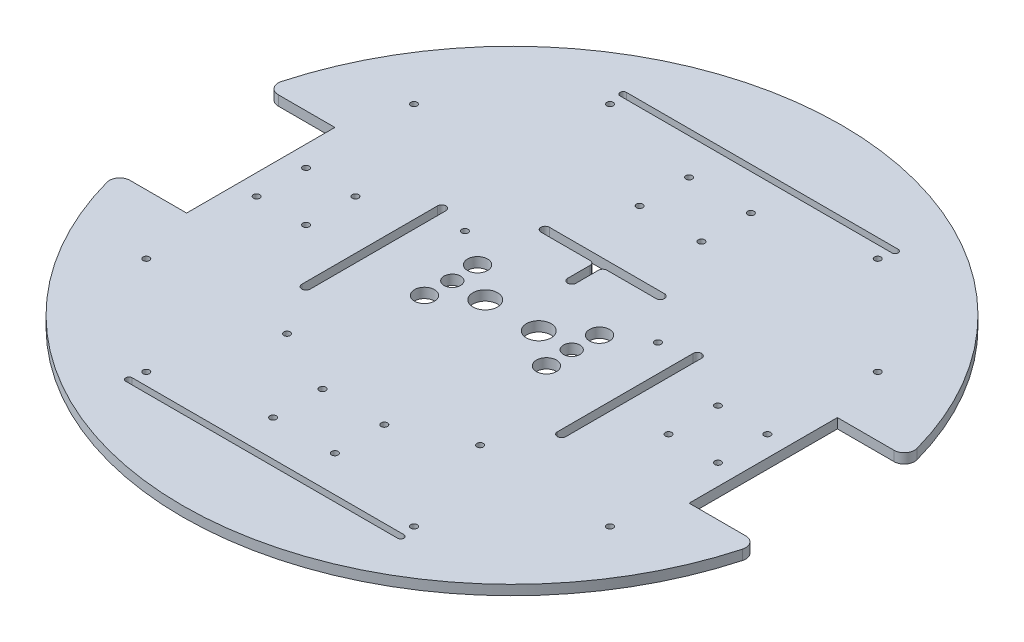
SolidWorks part; units mm, degrees
material "PMMA"
ref_plane "Front" through (0, 0, 0) normal (0, 0, 1) x (1, 0, 0)
ref_plane "Top" through (0, 0, 0) normal (0, 1, 0) x (1, 0, 0)
ref_plane "Right" through (0, 0, 0) normal (1, 0, 0) x (0, 0, -1)
sketch "草图1" plane through (0, 0, 0) normal (0, 1, 0) x (1, 0, 0)
  line L1 (160, 0) -> (80, 138.5641) construction
  line L2 (80, 138.5641) -> (-80, 138.5641) construction
  line L3 (-80, 138.5641) -> (-160, 0) construction
  line L4 (-160, 0) -> (-80, -138.5641) construction
  line L5 (-80, -138.5641) -> (80, -138.5641) construction
  line L6 (80, -138.5641) -> (160, 0) construction
  circle A0 centre (0, 0) radius 160 construction
  circle A1 centre (0, 0) radius 160
  dimension "D1" = 320
extrude "凸台-拉伸1" add sketch "草图1" along normal blind 4.8
sketch "草图2" plane through (0, 0, 0) normal (0, 1, 0) x (1, 0, 0)
  line L0 (0, 184.3432) -> (0, -209.9123) construction
  line L1 (-276.6401, 0) -> (355.4455, 0) construction
  line L2 (46.86, 49.5976) -> (46.86, -71.1191) construction
  line L3 (122, 36) -> (162, 36)
  line L4 (122, 36) -> (122, -36)
  line L5 (122, -36) -> (162, -36)
  line L6 (162, 36) -> (162, -36)
  line L7 (-107.3452, -120) -> (223.7804, -120) construction
  line L8 (-46.86, 49.5976) -> (-46.86, -71.1191) construction
  line L9 (-162, 36) -> (-162, -36)
  line L10 (-122, -36) -> (-162, -36)
  line L11 (-122, 36) -> (-122, -36)
  line L12 (-122, 36) -> (-162, 36)
  line L13 (-107.3452, 120) -> (223.7804, 120) construction
  line L14 (0, 0) -> (-188.9173, 109.0714) construction
  line L15 (67.5, 120) -> (32.5, 120) construction
  line L16 (0, 0) -> (-188.9173, -109.0714) construction
  line L17 (-67.5, -121.525) -> (-32.5, -121.525)
  line L18 (-67.5, -121.525) -> (-67.5, -118.475)
  line L19 (-67.5, -118.475) -> (-32.5, -118.475)
  line L20 (0, 0) -> (188.9173, -109.0714) construction
  line L21 (0, 0) -> (188.9173, 109.0714) construction
  line L22 (-32.5, -121.525) -> (-32.5, -118.475)
  line L23 (-50, -118.475) -> (-50, -121.525) construction
  line L24 (-67.5, -120) -> (-32.5, -120) construction
  line L25 (-17.5, -121.525) -> (17.5, -121.525)
  line L26 (-17.5, -121.525) -> (-17.5, -118.475)
  line L27 (-17.5, -118.475) -> (17.5, -118.475)
  line L28 (17.5, -121.525) -> (17.5, -118.475)
  line L29 (0, -118.475) -> (0, -121.525) construction
  line L30 (-17.5, -120) -> (17.5, -120) construction
  line L31 (67.5, -121.525) -> (32.5, -121.525)
  line L32 (67.5, -121.525) -> (67.5, -118.475)
  line L33 (67.5, -118.475) -> (32.5, -118.475)
  line L34 (32.5, -121.525) -> (32.5, -118.475)
  line L35 (50, -118.475) -> (50, -121.525) construction
  line L36 (67.5, -120) -> (32.5, -120) construction
  line L37 (50, 118.475) -> (50, 121.525) construction
  line L38 (-17.5, 120) -> (17.5, 120) construction
  line L39 (0, 118.475) -> (0, 121.525) construction
  line L40 (-67.5, 120) -> (-32.5, 120) construction
  line L41 (-50, 118.475) -> (-50, 121.525) construction
  line L42 (32.5, 121.525) -> (32.5, 118.475)
  line L43 (67.5, 118.475) -> (32.5, 118.475)
  line L44 (67.5, 121.525) -> (67.5, 118.475)
  line L45 (67.5, 121.525) -> (32.5, 121.525)
  line L46 (17.5, 121.525) -> (17.5, 118.475)
  line L47 (-17.5, 118.475) -> (17.5, 118.475)
  line L48 (-17.5, 121.525) -> (-17.5, 118.475)
  line L49 (-17.5, 121.525) -> (17.5, 121.525)
  line L50 (-32.5, 121.525) -> (-32.5, 118.475)
  line L51 (-67.5, 118.475) -> (-32.5, 118.475)
  line L52 (-67.5, 121.525) -> (-67.5, 118.475)
  line L53 (-67.5, 121.525) -> (-32.5, 121.525)
  circle A0 centre (112, 12) radius 1.55
  circle A1 centre (112, -12) radius 1.55
  circle A2 centre (88, 12) radius 1.55
  circle A3 centre (88, -12) radius 1.55
  circle A4 centre (13, 0) radius 6
  circle A5 centre (29, 0) radius 4
  circle A6 centre (46.86, 24) radius 1.55
  circle A7 centre (46.86, -62.36) radius 1.55
  circle A10 centre (-15, -101) radius 1.55
  circle A11 centre (15, -101) radius 1.55
  circle A12 centre (-15, -77) radius 1.55
  circle A13 centre (15, -77) radius 1.55
  circle A14 centre (-46.86, -62.36) radius 1.55
  circle A15 centre (-46.86, 24) radius 1.55
  circle A16 centre (-29, 0) radius 4
  circle A17 centre (-13, 0) radius 6
  circle A18 centre (-88, -12) radius 1.55
  circle A19 centre (-88, 12) radius 1.55
  circle A20 centre (-112, -12) radius 1.55
  circle A21 centre (-112, 12) radius 1.55
  circle A22 centre (15, 77) radius 1.55
  circle A23 centre (-15, 77) radius 1.55
  circle A24 centre (15, 101) radius 1.55
  circle A25 centre (-15, 101) radius 1.55
  point P27 (-50, -120)
  point P73 (0, -120)
  point P79 (50, -120)
  point P110 (50, 120)
  point P111 (0, 120)
  point P112 (-50, 120)
  dimension "D5" = 3.1
  dimension "D6" = 3.1
  dimension "D7" = 3.1
  dimension "D8" = 3.1
  dimension "D19" = 12
  dimension "D20" = 8
  dimension "D21" = 3.1
  dimension "D24" = 3.1
  dimension "D27" = 50
  dimension "D28" = 50
  dimension "D31" = 3.1
  dimension "D34" = 3.1
  dimension "D37" = 3.1
  dimension "D38" = 3.1
  dimension "D1" = 72
  dimension "D2" = 40
  dimension "D3" = 122
  dimension "D4" = 36
  dimension "D9" = 10
  dimension "D10" = 12
  dimension "D11" = 10
  dimension "D12" = 12
  dimension "D13" = 12
  dimension "D14" = 12
  dimension "D15" = 24
  dimension "D16" = 24
  dimension "D17" = 13
  dimension "D18" = 16
  dimension "D22" = 46.86
  dimension "D23" = 24
  dimension "D25" = 86.36
  dimension "D26" = 120
  dimension "D29" = 3.05
  dimension "D30" = 35
  dimension "D32" = 19
  dimension "D33" = 15
  dimension "D35" = 15
  dimension "D36" = 19
  dimension "D39" = 24
  dimension "D40" = 24
  dimension "D41" = 15
  dimension "D42" = 15
  dimension "D43" = 30
extrude "切除-拉伸1" cut sketch "草图2" against normal through all and the other way through all
sketch "草图3" plane through (0, 0, 0) normal (0, 1, 0) x (1, 0, 0)
  line L0 (0, 182.6235) -> (0, -187.0702) construction
  line L1 (-30, 46.1) -> (30, 46.1)
  line L2 (-30, 46.1) -> (-30, 42)
  line L3 (-30, 42) -> (-2.05, 42)
  line L4 (30, 46.1) -> (30, 42)
  line L5 (-150.5472, 0) -> (174.2648, 0) construction
  line L6 (-60, -40) -> (-64.1, -40)
  line L8 (-2.05, 42) -> (-2.05, 27)
  line L9 (-2.05, 27) -> (2.05, 27)
  line L10 (2.05, 42) -> (2.05, 27)
  line L11 (60, 30) -> (64.1, 30)
  line L12 (60, 30) -> (60, -40)
  line L13 (60, -40) -> (64.1, -40)
  line L14 (64.1, 30) -> (64.1, -40)
  line L19 (-60, 30) -> (-64.1, 30)
  line L20 (-64.1, 30) -> (-64.1, -40)
  line L21 (-60, 30) -> (-60, -40)
  line L22 (2.05, 42) -> (30, 42)
  point P7 (-30, 44.05)
  dimension "D1" = 4.1
  dimension "D2" = 60
  dimension "D3" = 30
  dimension "D4" = 42
  dimension "D5" = 4.1
  dimension "D6" = 15
  dimension "D7" = 2.05
  dimension "D8" = 4.1
  dimension "D9" = 70
  dimension "D10" = 30
  dimension "D11" = 60
extrude "切除-拉伸6" cut sketch "草图3" against normal through all and the other way through all
fillet "圆角3" radius 2.05 8 edges at (2.05, 2.4, -27) (-2.05, 2.4, -27) (30, 2.4, -42) (30, 2.4, -46.1) (2.05, 2.4, -42) (-2.05, 2.4, -42) (-30, 2.4, -42) (-30, 2.4, -46.1)
fillet "圆角6" radius 2.05 8 edges at (60, 2.4, 40) (64.1, 2.4, 40) (64.1, 2.4, -30) (60, 2.4, -30) (-60, 2.4, -30) (-60, 2.4, 40) (-64.1, 2.4, 40) (-64.1, 2.4, -30)
fillet "圆角7" radius 1.5 24 edges at (-67.5, 2.4, 121.525) (-67.5, 2.4, 118.475) (-32.5, 2.4, 121.525) (-32.5, 2.4, 118.475) (-17.5, 2.4, 121.525) (-17.5, 2.4, 118.475) (17.5, 2.4, 121.525) (17.5, 2.4, 118.475) (32.5, 2.4, 121.525) (32.5, 2.4, 118.475) (67.5, 2.4, 121.525) (67.5, 2.4, 118.475) (67.5, 2.4, -118.475) (67.5, 2.4, -121.525) (32.5, 2.4, -121.525) (32.5, 2.4, -118.475) (17.5, 2.4, -121.525) (17.5, 2.4, -118.475) (-17.5, 2.4, -118.475) (-17.5, 2.4, -121.525) (-32.5, 2.4, -121.525) (-32.5, 2.4, -118.475) (-67.5, 2.4, -118.475) (-67.5, 2.4, -121.525)
fillet "圆角8" radius 5 4 edges at (-155.8974, 2.4, 36) (-155.8974, 2.4, -36) (155.8974, 2.4, 36) (155.8974, 2.4, -36)
sketch "草图4" plane through (0, 4.8, 0) normal (0, 1, 0) x (1, 0, 0)
  line L0 (0, 0) -> (0, 157.1329) construction
  line L1 (140.3176, 0) -> (-140.3176, 0) construction
  line L2 (16, 121.525) -> (-16, 121.525) construction
  line L3 (15.1038, 121.525) -> (36.7767, 121.525)
  line L4 (15.1038, 121.525) -> (15.1038, 118.475)
  line L5 (15.1038, 118.475) -> (36.7767, 118.475)
  line L6 (36.7767, 121.525) -> (36.7767, 118.475)
  line L7 (34, 118.475) -> (66, 118.475) construction
  line L8 (36.7767, -121.525) -> (36.7767, -118.475)
  line L9 (15.1038, -118.475) -> (36.7767, -118.475)
  line L10 (15.1038, -121.525) -> (15.1038, -118.475)
  line L11 (15.1038, -121.525) -> (36.7767, -121.525)
  line L12 (-15.1038, -121.525) -> (-36.7767, -121.525)
  line L13 (-15.1038, -121.525) -> (-15.1038, -118.475)
  line L14 (-15.1038, -118.475) -> (-36.7767, -118.475)
  line L15 (-36.7767, -121.525) -> (-36.7767, -118.475)
  line L16 (-36.7767, 121.525) -> (-36.7767, 118.475)
  line L17 (-15.1038, 118.475) -> (-36.7767, 118.475)
  line L18 (-15.1038, 121.525) -> (-15.1038, 118.475)
  line L19 (-15.1038, 121.525) -> (-36.7767, 121.525)
  circle A0 centre (29.6142, 12.8871) radius 4.8665
  circle A1 centre (112.5833, 65) radius 1.55
  circle A2 centre (65, 112.5833) radius 1.55
  circle A3 centre (65, -112.5833) radius 1.55
  circle A4 centre (112.5833, -65) radius 1.55
  circle A5 centre (29.6142, -12.8871) radius 4.8665
  circle A6 centre (-29.6142, -12.8871) radius 4.8665
  circle A7 centre (-112.5833, -65) radius 1.55
  circle A8 centre (-65, -112.5833) radius 1.55
  circle A9 centre (-65, 112.5833) radius 1.55
  circle A10 centre (-112.5833, 65) radius 1.55
  circle A11 centre (-29.6142, 12.8871) radius 4.8665
  point P7 (0, 0)
  point P18 (0, 0)
  point P19 (0, 0)
extrude "切除-拉伸7" cut sketch "草图4" against normal blind 10
